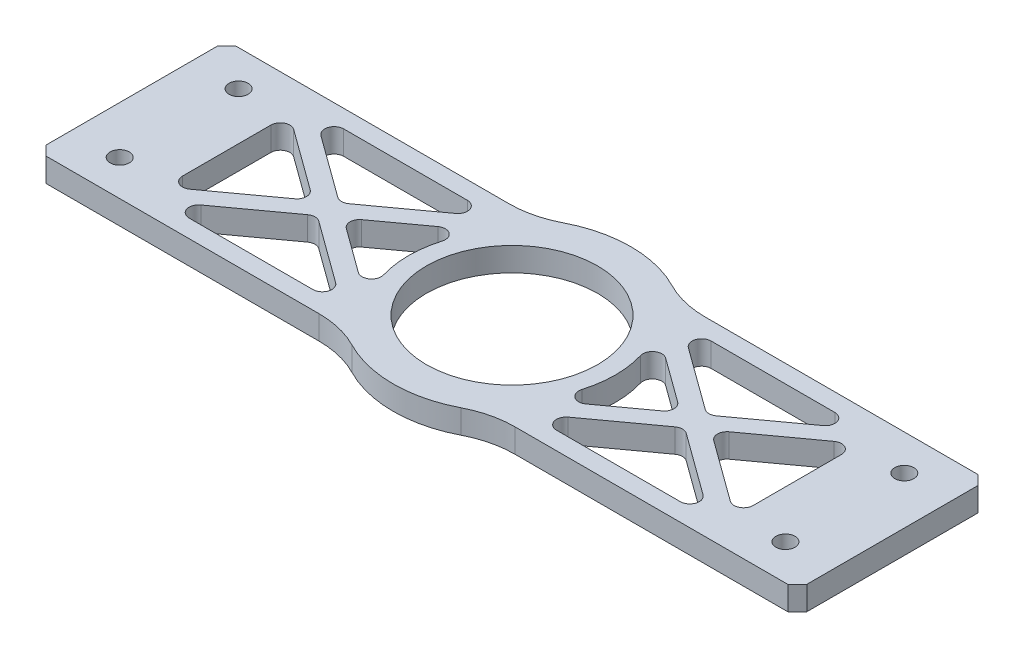
SolidWorks part; units mm, degrees
material "6061-T6 (SS)"
ref_plane "Front" through (0, 0, 0) normal (0, 0, 1) x (1, 0, 0)
ref_plane "Top" through (0, 0, 0) normal (0, 1, 0) x (1, 0, 0)
ref_plane "Right" through (0, 0, 0) normal (1, 0, 0) x (0, 0, -1)
sketch "Sketch1" plane through (0, 0, 0) normal (0, 1, 0) x (1, 0, 0)
  line L0 (203.2, 0) -> (203.2, 19.05) construction
  line L1 (0, 0) -> (75.4183, 0)
  line L2 (0, 0) -> (0, 50.8)
  line L3 (0, 50.8) -> (75.4183, 50.8)
  line L4 (203.2, 0) -> (203.2, 50.8)
  line L5 (0, 50.8) -> (203.2, 0) construction
  line L6 (127.7817, 50.8) -> (203.2, 50.8)
  line L7 (127.7817, 0) -> (203.2, 0)
  arc A0 (87.0546, -2.8222) -> (116.1454, -2.8222) centre (101.6, 25.4) ccw
  arc A1 (116.1454, 53.6222) -> (87.0546, 53.6222) centre (101.6, 25.4) ccw
  arc A2 (75.4183, 0) -> (87.0546, -2.8222) centre (75.4183, -25.4) cw
  arc A3 (127.7817, 0) -> (116.1454, -2.8222) centre (127.7817, -25.4) ccw
  arc A4 (127.7817, 50.8) -> (116.1454, 53.6222) centre (127.7817, 76.2) cw
  arc A5 (75.4183, 50.8) -> (87.0546, 53.6222) centre (75.4183, 76.2) ccw
  point P18 (120.65, 50.8)
  dimension "D2" = 63.5
  dimension "D3" = 25.4
  dimension "D1" = 50.8
extrude "Boss-Extrude1" add sketch "Sketch1" along normal blind 6.35
sketch "Sketch4" plane through (0, 6.35, 0) normal (0, 1, 0) x (1, 0, 0)
  line L0 (0, 0) -> (12.7, 9.525) construction
  line L1 (0, 0) -> (75.4183, 0) construction
  line L6 (12.7, 9.525) -> (12.7, 41.275) construction
  line L7 (12.7, 41.275) -> (25.4, 50.8) construction
  line L8 (75.4183, 50.8) -> (0, 50.8) construction
  line L9 (101.6, 0) -> (101.6, 25.4) construction
  arc A0 (87.0546, -2.8222) -> (116.1454, -2.8222) centre (101.6, 25.4) ccw construction
  point P0 (12.7, 41.275)
  point P4 (12.7, 9.525)
  point P34 (190.5, 9.525)
  point P36 (190.5, 41.275)
  dimension "D1" = 31.75
  dimension "D2" = 25.4
hole_wizard "#10 Clearance Hole1" positions "Sketch4" profile "Sketch3" hole size "#10" standard "ANSI Inch" end condition up to next
sketch "Sketch3" plane through (12.7, 6.35, -41.275) normal (1, 0, 0) x (0, 0, 1)
  line L0 (0, 0) -> (0, 6.35)
  line L1 (0, 6.35) -> (2.5527, 6.35)
  line L2 (2.5527, 6.35) -> (2.5527, 0)
  line L5 (2.5527, 0) -> (0, 0)
  line L11 (0, -6.35) -> (0, 107.95) construction
  dimension "Thru Hole Dia." = 5.1054
  dimension "Thru Hole Depth" = 6.35
sketch "Sketch5" plane through (0, 6.35, 0) normal (0, 1, 0) x (1, 0, 0)
  circle A0 centre (101.6, 25.4) radius 22.86
  arc A1 (116.1454, 53.6222) -> (87.0546, 53.6222) centre (101.6, 25.4) ccw construction
  dimension "D1" = 45.72
extrude "Cut-Extrude1" cut sketch "Sketch5" against normal through all
chamfer "Chamfer1" distance 2.54 angle 45 4 edges at (0, 3.175, -50.8) (203.2, 3.175, -50.8) (203.2, 3.175, 0) (0, 3.175, 0)
sketch "Sketch6" plane through (0, 6.35, 0) normal (0, 1, 0) x (1, 0, 0)
  line L1 (28.201, 46.0375) -> (76.8618, 46.0375)
  line L2 (25.4, 42.1858) -> (25.4, 8.6142)
  line L3 (28.201, 4.7625) -> (76.8618, 4.7625)
  line L9 (0, 48.26) -> (0, 2.54) construction
  line L10 (75.4183, 50.8) -> (2.54, 50.8) construction
  line L11 (2.54, 0) -> (75.4183, 0) construction
  line L14 (28.201, 46.0375) -> (52.5314, 28.3443)
  line L15 (76.8618, 4.7625) -> (52.5314, 22.4557)
  line L16 (76.8618, 46.0375) -> (52.5314, 28.3443)
  line L17 (28.201, 4.7625) -> (52.5314, 22.4557)
  line L18 (48.4826, 25.4) -> (25.4, 8.6142)
  line L19 (56.5802, 25.4) -> (79.6628, 42.1858)
  line L20 (56.5802, 25.4) -> (79.6628, 8.6142)
  line L21 (48.4826, 25.4) -> (25.4, 42.1858)
  line L22 (28.201, 46.0375) -> (25.4, 42.1858) construction
  line L23 (101.6, 25.4) -> (101.6, 40.5586) construction
  line L24 (76.8618, 4.7625) -> (79.6628, 8.6142) construction
  line L25 (154.7174, 25.4) -> (177.8, 42.1858)
  line L26 (146.6198, 25.4) -> (123.5372, 8.6142)
  line L27 (146.6198, 25.4) -> (123.5372, 42.1858)
  line L28 (154.7174, 25.4) -> (177.8, 8.6142)
  line L29 (174.999, 4.7625) -> (150.6686, 22.4557)
  line L30 (126.3382, 46.0375) -> (150.6686, 28.3443)
  line L31 (126.3382, 4.7625) -> (150.6686, 22.4557)
  line L32 (174.999, 46.0375) -> (150.6686, 28.3443)
  line L33 (174.999, 4.7625) -> (126.3382, 4.7625)
  line L34 (177.8, 42.1858) -> (177.8, 8.6142)
  line L35 (174.999, 46.0375) -> (126.3382, 46.0375)
  circle A6 centre (101.6, 25.4) radius 27.6225
  arc A7 (79.6628, 42.1858) -> (79.6628, 8.6142) centre (101.6, 25.4) ccw
  arc A8 (123.5372, 42.1858) -> (123.5372, 8.6142) centre (101.6, 25.4) cw
  dimension "D7" = 4.7625
  dimension "D1" = 4.7625
  dimension "D2" = 25.4
  dimension "D3" = 4.7625
  dimension "D4" = 4.7625
extrude "Cut-Extrude2" cut sketch "Sketch6" against normal through all
fillet "Fillet1" radius 2.54 24 edges at (76.8618, 3.175, -46.0375) (52.5314, 3.175, -28.3443) (150.6686, 3.175, -22.4557) (174.999, 3.175, -4.7625) (126.3382, 3.175, -4.7625) (177.8, 3.175, -42.1858) (177.8, 3.175, -8.6142) (154.7174, 3.175, -25.4) (150.6686, 3.175, -28.3443) (126.3382, 3.175, -46.0375) (174.999, 3.175, -46.0375) (28.201, 3.175, -4.7625) (52.5314, 3.175, -22.4557) (76.8618, 3.175, -4.7625) (56.5802, 3.175, -25.4) (79.6628, 3.175, -42.1858) (79.6628, 3.175, -8.6142) (25.4, 3.175, -42.1858) (48.4826, 3.175, -25.4) (25.4, 3.175, -8.6142) (146.6198, 3.175, -25.4) (123.5372, 3.175, -8.6142) (123.5372, 3.175, -42.1858) (28.201, 3.175, -46.0375)
